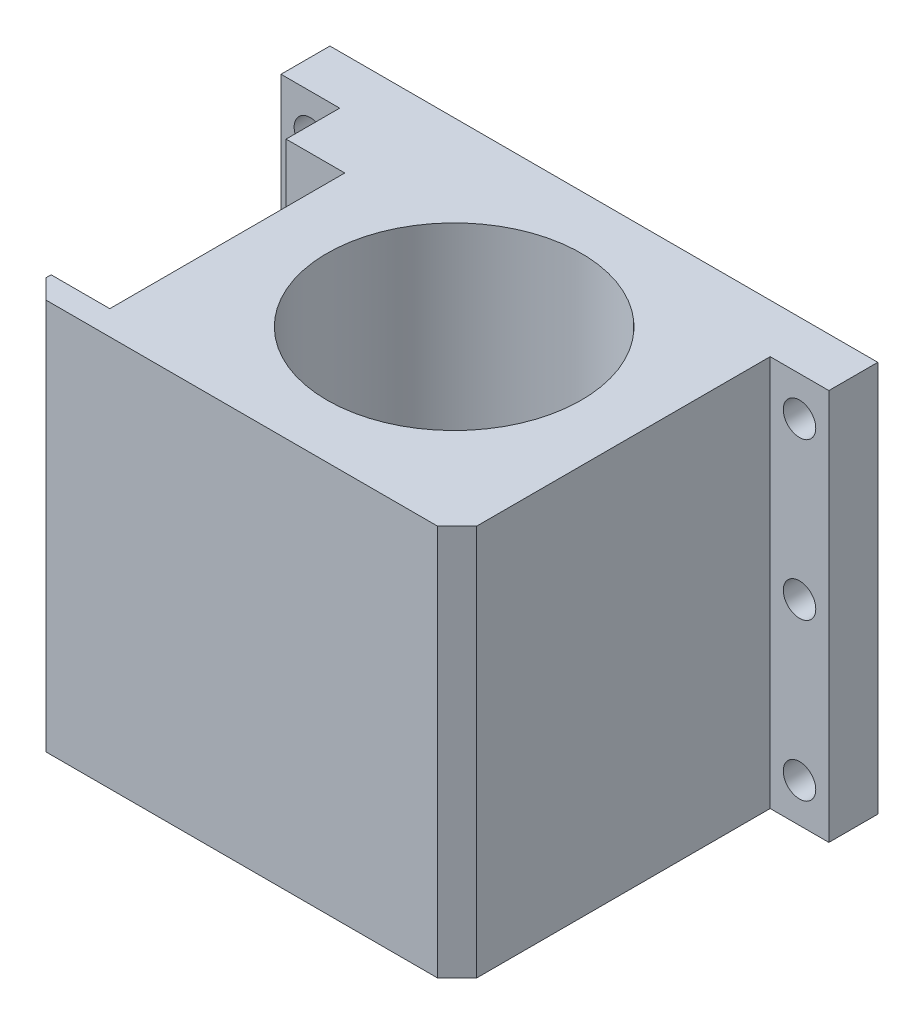
SolidWorks part; units mm, degrees
material "3.3315 (EN-AW 5005)"
ref_plane "前视基准面" through (0, 0, 0) normal (0, 0, 1) x (1, 0, 0)
ref_plane "上视基准面" through (0, 0, 0) normal (0, 1, 0) x (1, 0, 0)
ref_plane "右视基准面" through (0, 0, 0) normal (1, 0, 0) x (0, 0, -1)
other "Configuration Table"
sketch "草图1" plane through (0, 0, 0) normal (0, 0, 1) x (1, 0, 0)
  line L1 (0, 0) -> (140, 0)
  line L2 (0, 0) -> (0, -100)
  line L3 (0, -100) -> (140, -100)
  line L4 (140, 0) -> (140, -100)
  dimension "D1" = 140
  dimension "D2" = 100
extrude "凸台-拉伸1" add sketch "草图1" along normal blind 92.5
sketch "草图2" plane through (0, 0, 0) normal (0, 1, 0) x (1, 0, 0)
  line L0 (140, -46.25) -> (0, -46.25) construction
  line L1 (140, -92.5) -> (140, 0) construction
  line L2 (0, -92.5) -> (0, 0) construction
  circle A0 centre (78, -46.25) radius 32.5
  dimension "D1" = 65
  dimension "D2" = 62
extrude "切除-拉伸1" cut sketch "草图2" against normal through all
sketch "草图3" plane through (0, 0, 92.5) normal (0, 0, 1) x (1, 0, 0)
  line L0 (70, 0) -> (70, -100) construction
  line L1 (140, 0) -> (0, 0) construction
  line L2 (0, -100) -> (140, -100) construction
  line L3 (0, 0) -> (0, -100) construction
  line L4 (15, 0) -> (125, 0)
  line L5 (15, 0) -> (15, -100)
  line L6 (15, -100) -> (125, -100)
  line L7 (125, 0) -> (125, -100)
  dimension "D1" = 110
  dimension "D2" = 15
extrude "切除-拉伸2" cut sketch "草图3" against normal blind 80 flip side to cut
sketch "草图4" plane through (0, 0, 0) normal (0, 1, 0) x (1, 0, 0)
  circle A0 centre (78, -46.25) radius 46 construction
  dimension "D1" = 92
sketch "草图5" plane through (15, 0, 0) normal (-1, 0, 0) x (0, 0, 1)
  line L0 (46.25, 0) -> (46.25, -100) construction
  line L1 (92.25, 0) -> (0.25, 0) construction
  line L2 (12.5, -100) -> (92.5, -100) construction
  line L4 (26.2, 0) -> (86.25, 0)
  line L5 (26.2, 0) -> (26.2, -100)
  line L6 (26.2, -100) -> (86.25, -100)
  line L7 (86.25, 0) -> (86.25, -100)
  dimension "D1" = 60.05
  dimension "D2" = 40
extrude "切除-拉伸3" cut sketch "草图5" against normal blind 15
chamfer "倒角2" distance 5 angle 45 2 edges at (125, -50, 92.5) (15, -50, 92.5)
sketch "草图6" plane through (0, -100, 0) normal (0, -1, 0) x (1, 0, 0)
  line L0 (78, 46.25) -> (78, 92.25) construction
  circle A0 centre (78, 46.25) radius 39.5 construction
  circle A1 centre (78, 46.25) radius 46 construction
  circle A2 centre (78, 85.75) radius 2.6
  circle A3 centre (112.208, 66) radius 2.6
  circle A4 centre (112.208, 26.5) radius 2.6
  circle A5 centre (78, 6.75) radius 2.6
  circle A6 centre (43.792, 26.5) radius 2.6
  circle A7 centre (43.792, 66) radius 2.6
  point P20 (78, 46.25)
  dimension "D1" = 79
  dimension "D2" = 5.2
  dimension "D3" = 6
extrude "切除-拉伸4" cut sketch "草图6" against normal blind 20
sketch "草图9" plane through (0, 0, 12.5) normal (0, 0, 1) x (1, 0, 0)
  line L0 (0, 0) -> (0, -100) construction
  line L1 (15, 0) -> (0, 0) construction
  circle A0 centre (7.5, -10) radius 4.15
  circle A1 centre (132.5, -10) radius 4.15
  circle A2 centre (132.5, -50) radius 4.15
  circle A3 centre (132.5, -90) radius 4.15
  circle A4 centre (7.5, -50) radius 4.15
  circle A5 centre (7.5, -90) radius 4.15
  dimension "D1" = 8.3
  dimension "D4" = 2
  dimension "D2" = 7.5
  dimension "D3" = 10
  dimension "D5" = 3
extrude "切除-拉伸5" cut sketch "草图9" against normal through all
